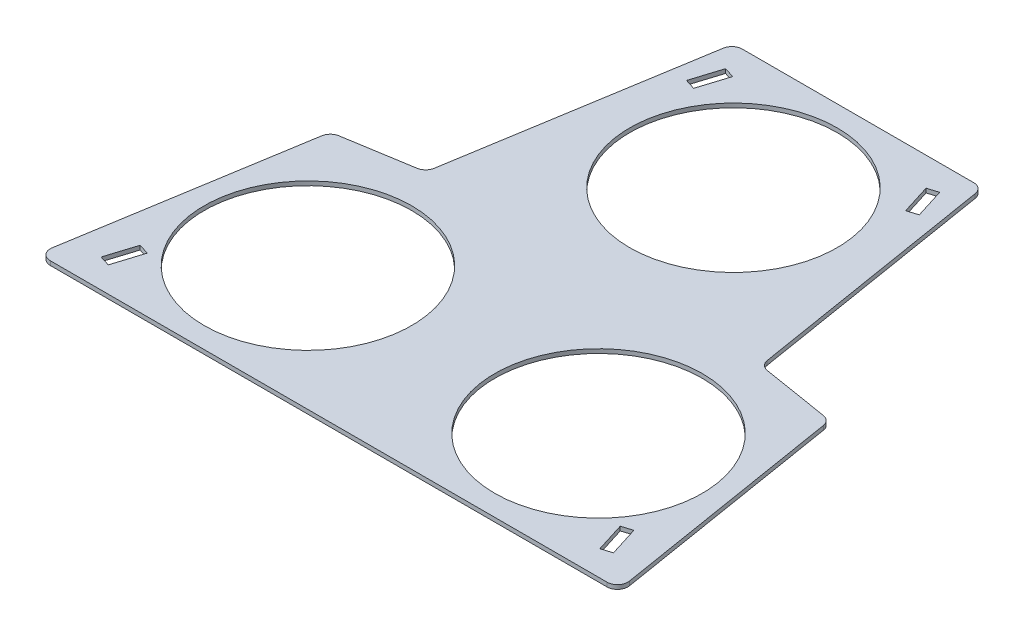
SolidWorks part; units mm, degrees
material "Acrylic (Medium-high impact)"
ref_plane "Front Plane" through (0, 0, 0) normal (0, 0, 1) x (1, 0, 0)
ref_plane "Top Plane" through (0, 0, 0) normal (0, 1, 0) x (1, 0, 0)
ref_plane "Right Plane" through (0, 0, 0) normal (1, 0, 0) x (0, 0, -1)
sketch "Sketch1" plane through (0, 0, 0) normal (0, 1, 0) x (1, 0, 0)
  line L0 (-134.1189, 0) -> (134.1189, 0)
  line L1 (139.0537, 5.8045) -> (120.843, 117.5127)
  line L2 (116.7126, 121.6431) -> (84.3366, 126.921)
  line L3 (80.2062, 131.0514) -> (60.684, 250.8045)
  line L4 (-55.7491, 255) -> (55.7491, 255)
  line L6 (-60.684, 250.8045) -> (-80.2062, 131.0514)
  line L7 (-84.3366, 126.921) -> (-116.7126, 121.6431)
  line L8 (-120.843, 117.5127) -> (-139.0537, 5.8045)
  line L9 (0, 0) -> (0, 255) construction
  circle A0 centre (0, 195) radius 50
  circle A1 centre (-70, 60) radius 50
  circle A2 centre (70, 60) radius 50
  arc A3 (-116.7126, 121.6431) -> (-120.843, 117.5127) centre (-115.9081, 116.7082) ccw
  arc A4 (-80.2062, 131.0514) -> (-84.3366, 126.921) centre (-85.1411, 131.8559) cw
  arc A5 (84.3366, 126.921) -> (80.2062, 131.0514) centre (85.1411, 131.8559) cw
  arc A6 (120.843, 117.5127) -> (116.7126, 121.6431) centre (115.9081, 116.7082) ccw
  arc A7 (134.1189, 0) -> (139.0537, 5.8045) centre (134.1189, 5) ccw
  arc A8 (60.684, 250.8045) -> (55.7491, 255) centre (55.7491, 250) ccw
  arc A9 (-55.7491, 255) -> (-60.684, 250.8045) centre (-55.7491, 250) ccw
  arc A10 (-139.0537, 5.8045) -> (-134.1189, 0) centre (-134.1189, 5) ccw
  point P19 (-120.264, 121.0641)
  point P22 (-80.7852, 127.5)
  point P25 (80.7852, 127.5)
  point P28 (120.264, 121.0641)
  point P31 (140, 0)
  point P34 (60, 255)
  point P37 (-60, 255)
  point P40 (-140, 0)
  dimension "D1" = 100
  dimension "D2" = 100
  dimension "D3" = 100
  dimension "D12" = 5
  dimension "D4" = 60
  dimension "D5" = 60
  dimension "D6" = 140
  dimension "D7" = 135
  dimension "D8" = 127.5
  dimension "D9" = 280
  dimension "D10" = 120
  dimension "D11" = 40
extrude "Boss-Extrude1" add sketch "Sketch1" along normal blind 2
sketch "Sketch2" plane through (0, 2, 0) normal (0, 1, 0) x (1, 0, 0)
  line L0 (0, 0) -> (0, 255) construction
  line L1 (55.7491, 255) -> (-55.7491, 255) construction
  line L2 (-125, 0) -> (-45, 255) construction
  line L3 (-56.0739, 228.4711) -> (-51.5838, 242.7833)
  line L4 (-134.1189, 0) -> (134.1189, 0) construction
  line L5 (-56.0739, 228.4711) -> (-51.0647, 226.8996)
  line L6 (-51.5838, 242.7833) -> (-46.5746, 241.2118)
  line L7 (-51.0647, 226.8996) -> (-46.5746, 241.2118)
  line L8 (-56.0739, 228.4711) -> (-46.5746, 241.2118) construction
  line L9 (-51.5838, 242.7833) -> (-51.0647, 226.8996) construction
  line L10 (113.9261, 26.5289) -> (123.4254, 13.7882) construction
  line L11 (-118.4162, 12.2167) -> (-113.9261, 26.5289)
  line L12 (-118.4162, 12.2167) -> (-123.4254, 13.7882)
  line L13 (-113.9261, 26.5289) -> (-118.9353, 28.1004)
  line L14 (-123.4254, 13.7882) -> (-118.9353, 28.1004)
  line L15 (-118.4162, 12.2167) -> (-118.9353, 28.1004) construction
  line L16 (-113.9261, 26.5289) -> (-123.4254, 13.7882) construction
  line L17 (118.4162, 12.2167) -> (118.9353, 28.1004) construction
  line L18 (51.5838, 242.7833) -> (51.0647, 226.8996) construction
  line L19 (56.0739, 228.4711) -> (46.5746, 241.2118) construction
  line L20 (125, 0) -> (45, 255) construction
  line L21 (123.4254, 13.7882) -> (118.9353, 28.1004)
  line L22 (113.9261, 26.5289) -> (118.9353, 28.1004)
  line L23 (118.4162, 12.2167) -> (123.4254, 13.7882)
  line L24 (118.4162, 12.2167) -> (113.9261, 26.5289)
  line L25 (51.0647, 226.8996) -> (46.5746, 241.2118)
  line L26 (51.5838, 242.7833) -> (46.5746, 241.2118)
  line L27 (56.0739, 228.4711) -> (51.0647, 226.8996)
  line L28 (56.0739, 228.4711) -> (51.5838, 242.7833)
  line L29 (-85, 127.5) -> (-208.5894, 166.2732) construction
  point P10 (-51.3242, 234.8415)
  point P13 (-118.6758, 20.1585)
  point P31 (118.6758, 20.1585)
  point P32 (51.3242, 234.8415)
  dimension "D1" = 45
  dimension "D3" = 5.25
  dimension "D4" = 15
  dimension "D5" = 210
  dimension "D6" = 125
extrude "Cut-Extrude1" cut sketch "Sketch2" against normal blind 5
